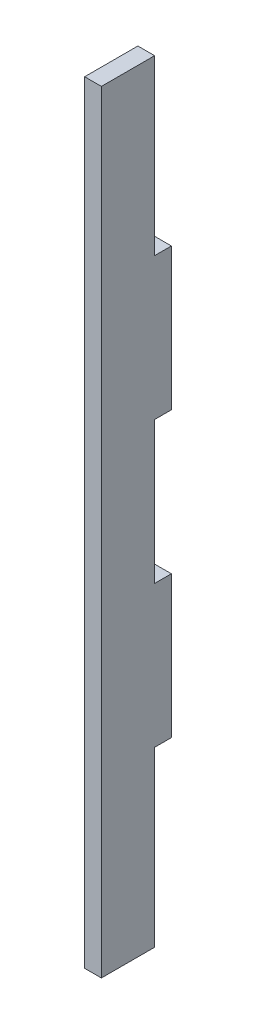
SolidWorks part; units mm, degrees
material "Acrylic (Medium-high impact)"
ref_plane "Front" through (0, 0, 0) normal (0, 0, 1) x (1, 0, 0)
ref_plane "Top" through (0, 0, 0) normal (0, 1, 0) x (1, 0, 0)
ref_plane "Right" through (0, 0, 0) normal (1, 0, 0) x (0, 0, -1)
sketch "Sketch1" plane through (0, 0, 0) normal (1, 0, 0) x (0, 0, -1)
  line L3 (-6.2611, -132.588) -> (6.2611, -132.588)
  line L69 (6.2611, 0) -> (6.2611, -132.588)
  line L70 (-6.2611, -132.588) -> (-6.2611, 0)
  line L71 (-6.2611, -127) -> (6.2611, -127) construction
  line L74 (4.7625, -25.4) -> (4.7625, -50.8) construction
  line L75 (4.7625, -76.2) -> (4.7625, -101.6) construction
  line L82 (6.2611, 0) -> (-6.2611, 0)
  line L83 (6.2611, 0) -> (6.2611, -25.4)
  line L84 (6.2611, 0) -> (3.2639, 0)
  line L85 (3.2639, 0) -> (3.2639, -25.4)
  line L86 (6.2611, -25.4) -> (3.2639, -25.4)
  line L87 (6.2611, -50.8) -> (6.2611, -76.2)
  line L88 (6.2611, -50.8) -> (3.2639, -50.8)
  line L89 (3.2639, -50.8) -> (3.2639, -76.2)
  line L90 (6.2611, -76.2) -> (3.2639, -76.2)
  line L96 (6.2611, -101.6) -> (3.2639, -101.6)
  line L97 (6.2611, -101.6) -> (6.2611, -127)
  line L98 (6.2611, -127) -> (3.2639, -127)
  line L99 (3.2639, -101.6) -> (3.2639, -127)
  line L101 (6.2611, -127) -> (3.2639, -127)
  line L102 (6.2611, -127) -> (6.2611, -132.588)
  line L103 (6.2611, -132.588) -> (3.2639, -132.588)
  line L104 (3.2639, -127) -> (3.2639, -132.588)
  line L106 (-6.2611, 0) -> (3.2639, 0)
  line L107 (-6.2611, 0) -> (-6.2611, 5.588)
  line L108 (-6.2611, 5.588) -> (3.2639, 5.588)
  line L109 (3.2639, 0) -> (3.2639, 5.588)
  point P4 (0, -132.588)
  dimension "D2" = 25.4
  dimension "D4" = 2.9972
  dimension "D1" = 25.4
  dimension "D5" = 9.525
  dimension "D3" = 5.588
extrude "Boss-Extrude1" add sketch "Sketch1" along normal blind 2.9972
sketch "Sketch2" [suppressed] plane through (3.175, 0, 0) normal (1, 0, 0) x (0, 0, -1)
  line L6 (6.35, -70.0024) -> (18.542, -70.0024)
  line L7 (6.35, -70.0024) -> (6.35, -85.9536)
  line L8 (6.35, -85.9536) -> (18.542, -85.9536)
  line L9 (18.542, -70.0024) -> (18.542, -85.9536)
  line L11 (6.35, -76.3905) -> (12.192, -76.3905)
  line L12 (6.35, -76.3905) -> (6.35, -79.5655)
  line L13 (6.35, -79.5655) -> (12.192, -79.5655)
  line L14 (12.192, -76.3905) -> (12.192, -79.5655)
  line L31 (6.35, -70.0024) -> (3.175, -70.0024) construction
  point P22 (12.192, -77.978)
  point P27 (18.542, -77.978)
  dimension "D1" = 12.192
  dimension "D3" = 3.175
  dimension "D4" = 5.842
extrude "Boss-Extrude2" [suppressed] add sketch "Sketch2" against normal up to surface (2.9972 mm away) up to face at (0, -63.5, -2.6755)
equation "\"bottomThickness\"= .220in"
equation "\"wallThickness\"= .118in"
equation "\"D4@Sketch1\"=\"wallThickness\""
equation "\"D1@Boss-Extrude1\"=\"wallThickness\""
equation "\"D3@Sketch1\"=\"bottomThickness\""
